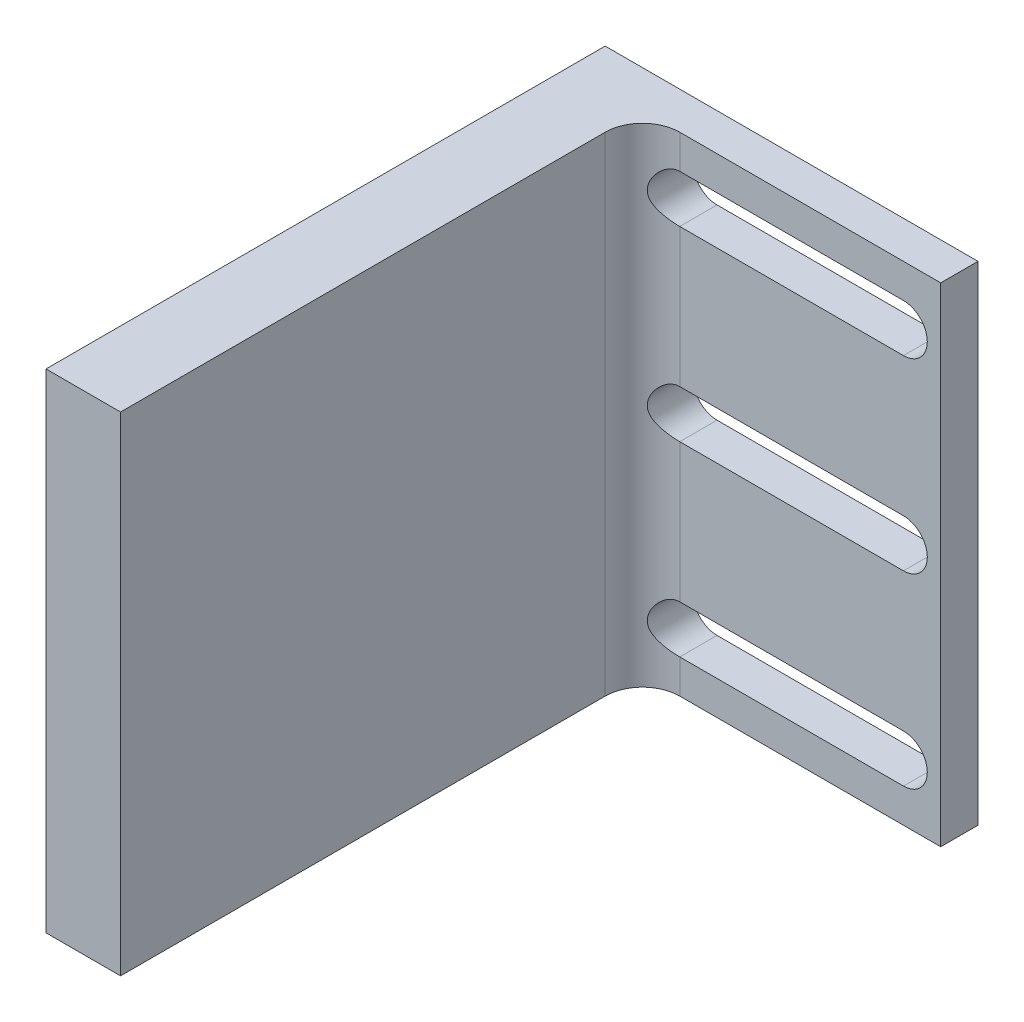
SolidWorks part; units mm, degrees
ref_plane "정면" through (0, 0, 0) normal (0, 0, 1) x (1, 0, 0)
ref_plane "윗면" through (0, 0, 0) normal (0, 1, 0) x (1, 0, 0)
ref_plane "우측면" through (0, 0, 0) normal (1, 0, 0) x (0, 0, -1)
sketch "스케치1" plane through (0, 0, 0) normal (0, 0, 1) x (1, 0, 0)
  line L1 (-25, -32.75) -> (25, -32.75)
  line L2 (-25, -32.75) -> (-25, 32.75)
  line L3 (-25, 32.75) -> (25, 32.75)
  line L4 (25, -32.75) -> (25, 32.75)
  line L5 (-25, -32.75) -> (25, 32.75) construction
  line L6 (-25, 32.75) -> (25, -32.75) construction
  point P0 (0, 0)
extrude "보스-돌출1" add sketch "스케치1" along normal blind 5
sketch "스케치4" plane through (0, 0, 5) normal (0, 0, 1) x (1, 0, 0)
  line L1 (-25, -32.75) -> (-15, -32.75)
  line L2 (-25, -32.75) -> (-25, 32.75)
  line L3 (-25, 32.75) -> (-15, 32.75)
  line L4 (-15, -32.75) -> (-15, 32.75)
  point P7 (0, 0)
extrude "보스-돌출2" add sketch "스케치4" along normal blind 70
sketch "스케치2" plane through (0, 0, 5) normal (0, 0, 1) x (1, 0, 0)
  line L0 (-15, -32.75) -> (25, -32.75) construction
  line L1 (25, -32.75) -> (25, 32.75) construction
  line L2 (-10, -28.2) -> (20, -28.2)
  line L3 (-10, -21.8) -> (20, -21.8)
  line L4 (-10, -3.2) -> (20, -3.2)
  line L5 (-10, 3.2) -> (20, 3.2)
  line L6 (-10, 21.8) -> (20, 21.8)
  line L7 (-10, 28.2) -> (20, 28.2)
  arc A0 (20, 21.8) -> (20, 28.2) centre (20, 25) ccw
  arc A1 (20, -3.2) -> (20, 3.2) centre (20, 0) ccw
  arc A2 (20, -28.2) -> (20, -21.8) centre (20, -25) ccw
  arc A3 (-10, -21.8) -> (-10, -28.2) centre (-10, -25) ccw
  arc A4 (-10, 3.2) -> (-10, -3.2) centre (-10, 0) ccw
  arc A5 (-10, 28.2) -> (-10, 21.8) centre (-10, 25) ccw
  dimension "D1" = 25
  dimension "D2" = 25
  dimension "D3" = 7.75
  dimension "D4" = 5
  dimension "D5" = 5
  dimension "D6" = 5
extrude "컷-돌출1" cut sketch "스케치2" against normal blind 5
fillet "필렛7" radius 5 1 edges at (-15, 0, 5)
